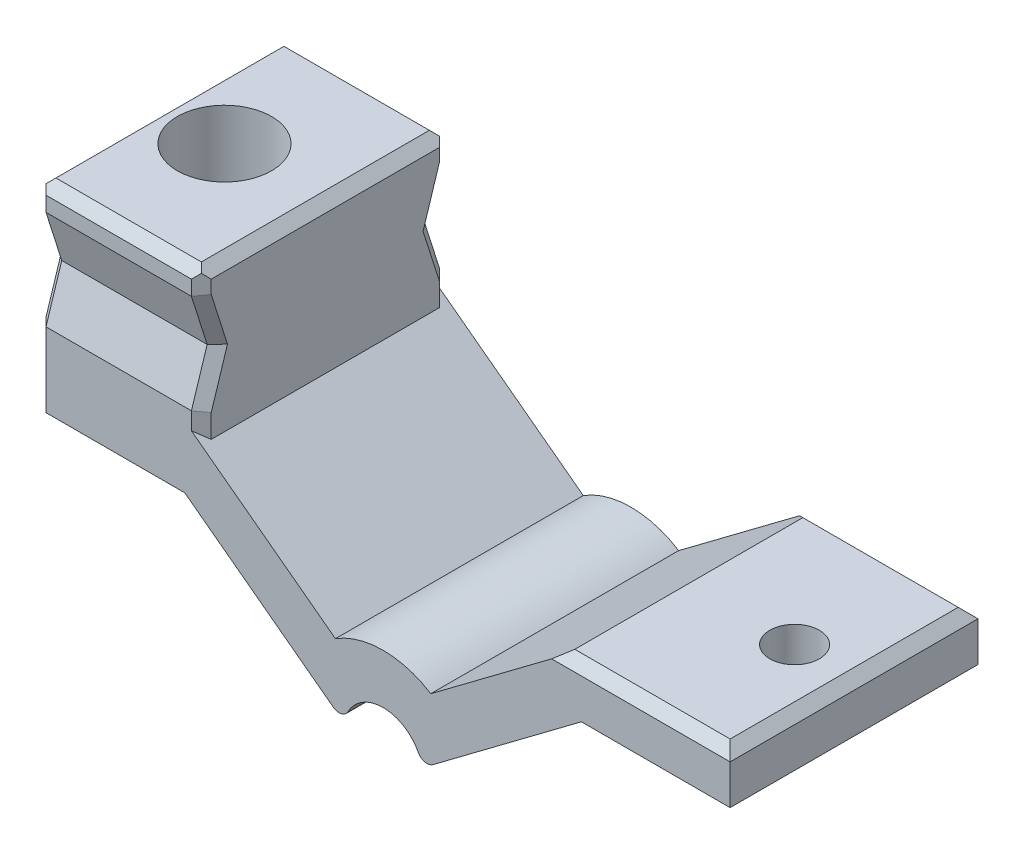
SolidWorks part; units mm, degrees
ref_plane "Front Plane" through (0, 0, 0) normal (0, 0, 1) x (1, 0, 0)
ref_plane "Top Plane" through (0, 0, 0) normal (0, 1, 0) x (1, 0, 0)
ref_plane "Right Plane" through (0, 0, 0) normal (1, 0, 0) x (0, 0, -1)
sketch "Sketch1" plane through (0, 0, 0) normal (0, 0, 1) x (1, 0, 0)
  line L0 (23.4838, 0.4259) -> (8.4838, 0.4259)
  line L1 (-7.5785, -11.6208) -> (8.4838, 0.4259)
  line L2 (-15.4539, -11.6208) -> (-31.5162, 0.4259)
  line L3 (-46.5162, 0.4259) -> (-31.5162, 0.4259)
  line L4 (-46.5162, 0.4259) -> (-46.5162, 20.4259)
  line L5 (-46.5162, 20.4259) -> (-29.8496, 20.4259)
  line L6 (23.4838, 5.4259) -> (6.8171, 5.4259)
  line L7 (-6.7067, -4.7169) -> (6.8171, 5.4259)
  line L8 (-16.3257, -4.7169) -> (-29.8496, 5.4259)
  line L9 (-29.8496, 20.4259) -> (-29.8496, 5.4259)
  line L10 (-46.5162, 20.4259) -> (-31.5162, 20.4259) construction
  line L11 (23.4838, 0.4259) -> (23.4838, 5.4259)
  line L18 (-41.5162, 5.4259) -> (-29.8496, 5.4259) construction
  line L19 (-41.5162, 5.4259) -> (-41.5162, 15.4259) construction
  line L20 (-41.5162, 15.4259) -> (-31.5162, 15.4259) construction
  arc A0 (-7.5785, -11.6208) -> (-15.4539, -11.6208) centre (-11.5162, -12.3241) ccw
  arc A1 (-6.7067, -4.7169) -> (-16.3257, -4.7169) centre (-11.5162, -12.3241) ccw
  dimension "D1" = 5
extrude "Boss-Extrude1" add sketch "Sketch1" along normal blind 25
fillet "Fillet1" radius 1 2 edges at (-15.4539, -11.6208, 12.5) (-7.5785, -11.6208, 12.5)
sketch "Sketch5" plane through (-29.8496, 0, 0) normal (1, 0, 0) x (0, 0, -1)
  line L2 (0, 7.9259) -> (0, 17.9259)
  line L5 (-12.5, 20.4259) -> (-12.5, 5.4259) construction
  line L14 (-25, 20.4259) -> (0, 20.4259) construction
  line L15 (-25, 5.4259) -> (0, 5.4259) construction
  line L19 (-25, 7.9259) -> (-25, 17.9259)
  line L20 (0, 17.9259) -> (-1.5869, 12.9259)
  line L21 (-1.5869, 12.9259) -> (0, 7.9259)
  line L22 (-25, 17.9259) -> (-23.4131, 12.9259)
  line L23 (-23.4131, 12.9259) -> (-25, 7.9259)
extrude "Cut-Extrude2" cut sketch "Sketch5" against normal through all
sketch "Sketch6" plane through (0, 20.4259, 0) normal (0, 1, 0) x (1, 0, 0)
  line L0 (-46.5162, 0) -> (-46.5162, -12.5) construction
  line L1 (-46.5162, -25) -> (-46.5162, 0) construction
  line L2 (-46.5162, -12.5) -> (-40.0162, -12.5) construction
hole_wizard "CBORE for M5 Hex Head Bolt1" positions "Sketch7" profile "Sketch8" counterbore size "M5" standard "ISO" end condition up to next
sketch "Sketch7" plane through (0, 20.4259, 0) normal (0, 1, 0) x (1, 0, 0)
  point P0 (-40.0162, -12.5)
sketch "Sketch8" plane through (-40.0162, 20.4259, 12.5) normal (1, 0, 0) x (0, 0, 1)
  line L0 (0, 0) -> (0, 20)
  line L1 (0, 20) -> (2.75, 20)
  line L3 (2.75, 20) -> (2.75, 15)
  line L4 (2.75, 15) -> (4.75, 15)
  line L5 (4.75, 15) -> (4.75, 0)
  line L7 (4.75, 0) -> (0, 0)
  line L11 (0, -6.35) -> (0, 107.95) construction
  dimension "Thru Hole Dia." = 5.5
  dimension "Thru Hole Depth" = 20
  dimension "C'Bore Dia." = 9.5
  dimension "C'Bore Depth" = 15
sketch "Sketch9" plane through (0, 5.4259, 0) normal (0, 1, 0) x (1, 0, 0)
  line L0 (23.4838, -12.5) -> (17.4838, -12.5) construction
  line L1 (23.4838, -25) -> (23.4838, 0) construction
hole_wizard "Ø5.0 (5) Diameter Hole1" positions "Sketch10" profile "Sketch11" hole size "Ø5.0" standard "ANSI Metric"
sketch "Sketch10" plane through (0, 5.4259, 0) normal (0, 1, 0) x (1, 0, 0)
  point P0 (17.4838, -12.5)
sketch "Sketch11" plane through (17.4838, 5.4259, 12.5) normal (1, 0, 0) x (0, 0, 1)
  line L0 (0, 0) -> (0, 16.5022)
  line L1 (0, 16.5022) -> (2.5, 15)
  line L2 (2.5, 15) -> (2.5, 0)
  line L5 (2.5, 0) -> (0, 0)
  line L10 (0, 16.5022) -> (-2.5, 15) construction
  line L11 (0, -6.35) -> (0, 107.95) construction
  dimension "Hole Dia." = 5
  dimension "Hole Depth" = 15
  dimension "Drill Angle" = 118
chamfer "Chamfer4" distance 1 angle 45 2 edges at (-46.5162, 20.4259, 12.5) (-29.8496, 20.4259, 12.5)
chamfer "Chamfer5" distance 1 angle 45 2 edges at (-38.1829, 20.4259, 25) (-38.1829, 20.4259, 0)
chamfer "Chamfer6" distance 1 angle 45 4 edges at (-46.5162, 4.1759, 0) (-46.5162, 10.4259, 0.7935) (-46.5162, 15.4259, 0.7935) (-46.5162, 18.6759, 0)
chamfer "Chamfer7" distance 1 angle 45 4 edges at (-46.5162, 4.1759, 25) (-46.5162, 10.4259, 24.2065) (-46.5162, 15.4259, 24.2065) (-46.5162, 18.6759, 25)
chamfer "Chamfer8" distance 1 angle 45 8 edges at (-29.8496, 6.6759, 25) (-29.8496, 10.4259, 24.2065) (-29.8496, 15.4259, 24.2065) (-29.8496, 18.6759, 25) (-29.8496, 6.6759, 0) (-29.8496, 10.4259, 0.7935) (-29.8496, 15.4259, 0.7935) (-29.8496, 18.6759, 0)
chamfer "Chamfer9" distance 1 angle 45 3 edges at (15.1504, 5.4259, 0) (23.4838, 5.4259, 12.5) (15.1504, 5.4259, 25)
